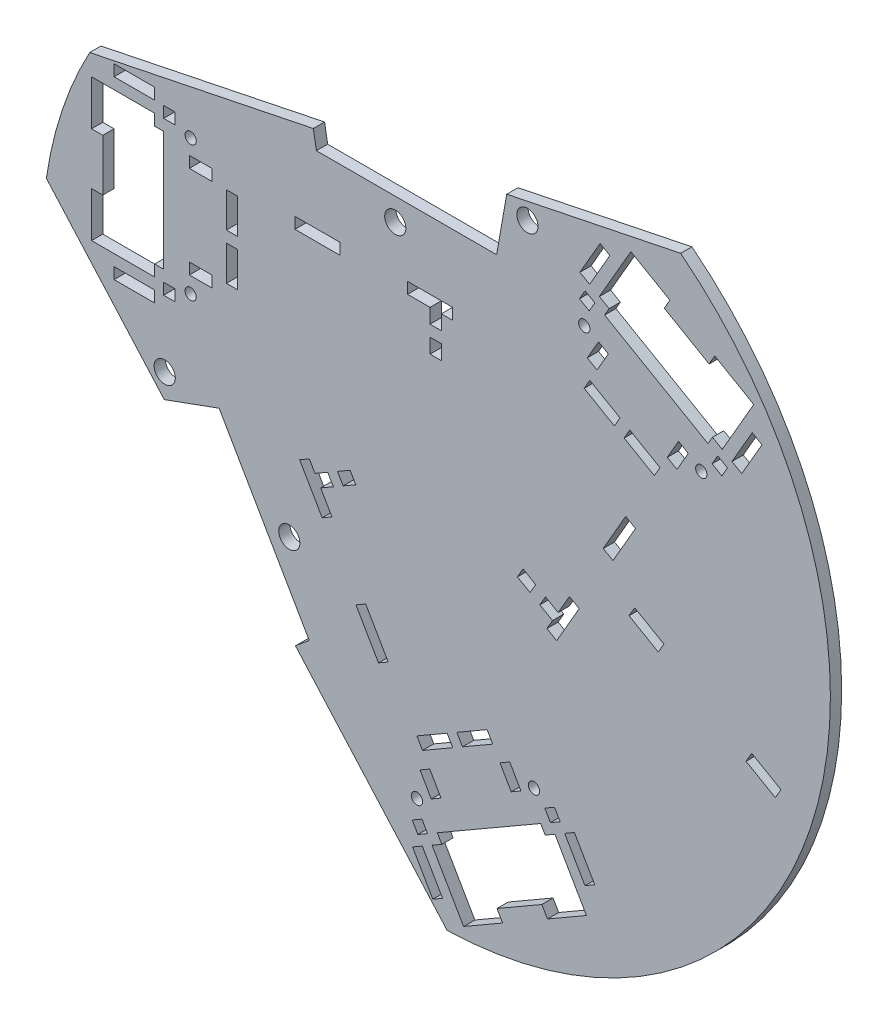
SolidWorks part; units mm, degrees
material "Balsa"
ref_plane "Plan de face" through (0, 0, 0) normal (0, 0, 1) x (1, 0, 0)
ref_plane "Plan de dessus" through (0, 0, 0) normal (0, 1, 0) x (1, 0, 0)
ref_plane "Plan de droite" through (0, 0, 0) normal (1, 0, 0) x (0, 0, -1)
sketch "Esquisse1" plane through (0, 0, 0) normal (0, 0, 1) x (1, 0, 0)
  circle A0 centre (148.0804, -12.1102) radius 175
extrude "Boss.-Extru.1" add sketch "Esquisse1" along normal blind 5
sketch "Esquisse2" plane through (0, 0, 0) normal (0, 0, -1) x (-1, 0, 0)
  line L0 (-155.3118, 53.7774) -> (-135.3118, 53.7774)
  line L1 (-150.3118, 37.2774) -> (-145.3118, 37.2774)
  line L2 (-150.3118, 37.2774) -> (-150.3118, 30.7774)
  line L3 (-150.3118, 30.7774) -> (-145.3118, 30.7774)
  line L4 (-145.3118, 37.2774) -> (-145.3118, 30.7774)
  line L5 (-105.3118, 53.7774) -> (-85.3118, 53.7774)
  line L6 (-105.3118, 53.7774) -> (-105.3118, 48.7774)
  line L7 (-105.3118, 48.7774) -> (-85.3118, 48.7774)
  line L8 (-85.3118, 53.7774) -> (-85.3118, 48.7774)
  line L9 (-59.86, 48.7774) -> (-54.86, 48.7774)
  line L10 (-59.86, 48.7774) -> (-59.86, 33.2774)
  line L11 (-59.86, 33.2774) -> (-54.86, 33.2774)
  line L12 (-54.86, 48.7774) -> (-54.86, 33.2774)
  line L13 (-59.86, 28.2774) -> (-54.86, 28.2774)
  line L14 (-59.86, 28.2774) -> (-59.86, 12.7774)
  line L15 (-59.86, 12.7774) -> (-54.86, 12.7774)
  line L16 (-54.86, 28.2774) -> (-54.86, 12.7774)
  line L17 (-48.43, 12.7774) -> (-38.43, 12.7774)
  line L18 (-48.43, 12.7774) -> (-48.43, 7.7774)
  line L19 (-48.43, 7.7774) -> (-38.43, 7.7774)
  line L20 (-38.43, 12.7774) -> (-38.43, 7.7774)
  line L21 (-32, -0.7226) -> (-27, -0.7226)
  line L22 (-32, -0.7226) -> (-32, -5.7226)
  line L23 (-32, -5.7226) -> (-27, -5.7226)
  line L24 (-27, -0.7226) -> (-27, -5.7226)
  line L25 (-23, -5.7226) -> (-5, -5.7226)
  line L26 (-23, -5.7226) -> (-23, -10.7226)
  line L27 (-23, -10.7226) -> (-5, -10.7226)
  line L28 (-5, -5.7226) -> (-5, -10.7226)
  line L29 (0, -0.7226) -> (5, -0.7226)
  line L30 (0, -0.7226) -> (0, 19.2774)
  line L31 (0, 19.2774) -> (5, 19.2774)
  line L32 (5, -0.7226) -> (5, 19.2774)
  line L33 (0, 42.2774) -> (5, 42.2774)
  line L34 (0, 42.2774) -> (0, 62.2774)
  line L35 (0, 62.2774) -> (5, 62.2774)
  line L36 (5, 42.2774) -> (5, 62.2774)
  line L37 (-23, 67.2774) -> (-5, 67.2774)
  line L38 (-23, 67.2774) -> (-23, 72.2774)
  line L39 (-23, 72.2774) -> (-5, 72.2774)
  line L40 (-5, 67.2774) -> (-5, 72.2774)
  line L41 (-27, 67.2774) -> (-32, 67.2774)
  line L42 (-27, 67.2774) -> (-27, 62.2774)
  line L43 (-27, 62.2774) -> (-32, 62.2774)
  line L44 (-32, 67.2774) -> (-32, 62.2774)
  line L45 (-38.43, 53.7774) -> (-48.43, 53.7774)
  line L46 (-38.43, 53.7774) -> (-38.43, 48.7774)
  line L47 (-38.43, 48.7774) -> (-48.43, 48.7774)
  line L48 (-48.43, 53.7774) -> (-48.43, 48.7774)
  line L49 (-135.3118, 53.7774) -> (-135.3118, 48.7774)
  line L50 (-135.3118, 48.7774) -> (-145.3118, 48.7774)
  line L51 (-135.3118, 48.7774) -> (-155.3118, 48.7774) construction
  line L52 (-145.3118, 48.7774) -> (-145.3118, 42.2774)
  line L53 (-145.3118, 42.2774) -> (-150.3118, 42.2774)
  line L54 (-150.3118, 42.2774) -> (-150.3118, 48.7774)
  line L55 (-150.3118, 48.7774) -> (-155.3118, 48.7774)
  line L56 (-155.3118, 48.7774) -> (-155.3118, 53.7774)
  line L57 (-87.4044, -38.7914) -> (-97.4044, -56.1119)
  line L58 (-104.1938, -34.8716) -> (-106.6938, -39.2017)
  line L59 (-104.1938, -34.8716) -> (-109.823, -31.6216)
  line L60 (-109.823, -31.6216) -> (-112.323, -35.9517)
  line L61 (-106.6938, -39.2017) -> (-112.323, -35.9517)
  line L62 (-112.4044, -82.0927) -> (-122.4044, -99.4132)
  line L63 (-112.4044, -82.0927) -> (-116.7345, -79.5927)
  line L64 (-116.7345, -79.5927) -> (-126.7345, -96.9132)
  line L65 (-122.4044, -99.4132) -> (-126.7345, -96.9132)
  line L66 (-139.4604, -118.9551) -> (-141.9604, -123.2852)
  line L67 (-139.4604, -118.9551) -> (-152.8838, -111.2051)
  line L68 (-152.8838, -111.2051) -> (-155.3838, -115.5352)
  line L69 (-141.9604, -123.2852) -> (-155.3838, -115.5352)
  line L70 (-157.2139, -108.7051) -> (-159.7139, -113.0352)
  line L71 (-157.2139, -108.7051) -> (-170.6373, -100.9551)
  line L72 (-170.6373, -100.9551) -> (-173.1373, -105.2852)
  line L73 (-159.7139, -113.0352) -> (-173.1373, -105.2852)
  line L74 (-176.3523, -110.8538) -> (-181.3523, -119.514)
  line L75 (-176.3523, -110.8538) -> (-180.6825, -108.3538)
  line L76 (-180.6825, -108.3538) -> (-185.6825, -117.014)
  line L77 (-181.3523, -119.514) -> (-185.6825, -117.014)
  line L78 (-196.2587, -118.3326) -> (-198.7587, -122.6627)
  line L79 (-196.2587, -118.3326) -> (-200.5888, -115.8326)
  line L80 (-200.5888, -115.8326) -> (-203.0888, -120.1627)
  line L81 (-198.7587, -122.6627) -> (-203.0888, -120.1627)
  line L82 (-205.0888, -123.6268) -> (-214.0888, -139.2153)
  line L83 (-205.0888, -123.6268) -> (-209.4189, -121.1268)
  line L84 (-209.4189, -121.1268) -> (-218.4189, -136.7153)
  line L85 (-214.0888, -139.2153) -> (-218.4189, -136.7153)
  line L86 (-212.2587, -146.0454) -> (-214.7587, -150.3755)
  line L87 (-212.2587, -146.0454) -> (-194.9382, -156.0454)
  line L88 (-194.9382, -156.0454) -> (-197.4382, -160.3755)
  line L89 (-214.7587, -150.3755) -> (-197.4382, -160.3755)
  line L90 (-175.0196, -167.5454) -> (-177.5196, -171.8755)
  line L91 (-175.0196, -167.5454) -> (-157.6991, -177.5454)
  line L92 (-157.6991, -177.5454) -> (-160.1991, -181.8755)
  line L93 (-177.5196, -171.8755) -> (-160.1991, -181.8755)
  line L94 (-141.869, -160.1268) -> (-150.869, -175.7153)
  line L95 (-141.869, -160.1268) -> (-137.5388, -162.6268)
  line L96 (-137.5388, -162.6268) -> (-146.5388, -178.2153)
  line L97 (-150.869, -175.7153) -> (-146.5388, -178.2153)
  line L98 (-139.869, -156.6627) -> (-137.369, -152.3326)
  line L99 (-139.869, -156.6627) -> (-144.1991, -154.1627)
  line L100 (-144.1991, -154.1627) -> (-141.6991, -149.8326)
  line L101 (-137.369, -152.3326) -> (-141.6991, -149.8326)
  line L102 (-145.8453, -140.014) -> (-140.8453, -131.3538)
  line L103 (-145.8453, -140.014) -> (-150.1754, -137.514)
  line L104 (-150.1754, -137.514) -> (-145.1754, -128.8538)
  line L105 (-140.8453, -131.3538) -> (-145.1754, -128.8538)
  line L106 (-97.4044, -56.1119) -> (-101.7345, -53.6119)
  line L107 (-101.7345, -53.6119) -> (-96.7345, -44.9517)
  line L108 (-96.7345, -44.9517) -> (-102.3637, -41.7017)
  line L109 (-102.3637, -41.7017) -> (-99.8637, -37.3716)
  line L110 (-99.8637, -37.3716) -> (-94.2345, -40.6216)
  line L111 (-94.2345, -40.6216) -> (-91.7345, -36.2914)
  line L112 (-91.7345, -36.2914) -> (-87.4044, -38.7914)
  line L113 (-201.5251, -51.3165) -> (-211.5251, -33.996)
  line L114 (-189.7357, -38.7364) -> (-192.2357, -34.4063)
  line L115 (-189.7357, -38.7364) -> (-184.1065, -35.4864)
  line L116 (-184.1065, -35.4864) -> (-186.6065, -31.1563)
  line L117 (-192.2357, -34.4063) -> (-186.6065, -31.1563)
  line L118 (-226.5251, -8.0153) -> (-236.5251, 9.3053)
  line L119 (-226.5251, -8.0153) -> (-222.195, -5.5153)
  line L120 (-222.195, -5.5153) -> (-232.195, 11.8053)
  line L121 (-236.5251, 9.3053) -> (-232.195, 11.8053)
  line L122 (-244.9209, 33.8472) -> (-247.4209, 38.1773)
  line L123 (-244.9209, 33.8472) -> (-231.4975, 41.5972)
  line L124 (-231.4975, 41.5972) -> (-233.9975, 45.9273)
  line L125 (-247.4209, 38.1773) -> (-233.9975, 45.9273)
  line L126 (-227.1673, 44.0972) -> (-229.6673, 48.4273)
  line L127 (-227.1673, 44.0972) -> (-213.7439, 51.8472)
  line L128 (-213.7439, 51.8472) -> (-216.2439, 56.1773)
  line L129 (-229.6673, 48.4273) -> (-216.2439, 56.1773)
  line L130 (-219.4589, 61.7458) -> (-224.4589, 70.4061)
  line L131 (-219.4589, 61.7458) -> (-215.1288, 64.2458)
  line L132 (-215.1288, 64.2458) -> (-220.1288, 72.9061)
  line L133 (-224.4589, 70.4061) -> (-220.1288, 72.9061)
  line L134 (-215.9826, 82.7246) -> (-218.4826, 87.0547)
  line L135 (-215.9826, 82.7246) -> (-211.6525, 85.2246)
  line L136 (-211.6525, 85.2246) -> (-214.1525, 89.5547)
  line L137 (-218.4826, 87.0547) -> (-214.1525, 89.5547)
  line L138 (-216.1525, 93.0188) -> (-225.1525, 108.6073)
  line L139 (-216.1525, 93.0188) -> (-211.8223, 95.5188)
  line L140 (-211.8223, 95.5188) -> (-220.8223, 111.1073)
  line L141 (-225.1525, 108.6073) -> (-220.8223, 111.1073)
  line L142 (-231.9826, 110.4374) -> (-234.4826, 114.7676)
  line L143 (-231.9826, 110.4374) -> (-249.3031, 100.4374)
  line L144 (-249.3031, 100.4374) -> (-251.8031, 104.7676)
  line L145 (-234.4826, 114.7676) -> (-251.8031, 104.7676)
  line L146 (-269.2217, 88.9374) -> (-271.7217, 93.2676)
  line L147 (-269.2217, 88.9374) -> (-286.5422, 78.9374)
  line L148 (-286.5422, 78.9374) -> (-289.0422, 83.2676)
  line L149 (-271.7217, 93.2676) -> (-289.0422, 83.2676)
  line L150 (-279.3723, 56.5188) -> (-288.3723, 72.1073)
  line L151 (-279.3723, 56.5188) -> (-283.7025, 54.0188)
  line L152 (-283.7025, 54.0188) -> (-292.7025, 69.6073)
  line L153 (-288.3723, 72.1073) -> (-292.7025, 69.6073)
  line L154 (-277.3723, 53.0547) -> (-274.8723, 48.7246)
  line L155 (-277.3723, 53.0547) -> (-273.0422, 55.5547)
  line L156 (-273.0422, 55.5547) -> (-270.5422, 51.2246)
  line L157 (-274.8723, 48.7246) -> (-270.5422, 51.2246)
  line L158 (-259.966, 49.9061) -> (-254.966, 41.2458)
  line L159 (-259.966, 49.9061) -> (-255.6359, 52.4061)
  line L160 (-255.6359, 52.4061) -> (-250.6359, 43.7458)
  line L161 (-254.966, 41.2458) -> (-250.6359, 43.7458)
  line L162 (-211.5251, -33.996) -> (-207.195, -31.496)
  line L163 (-207.195, -31.496) -> (-202.195, -40.1563)
  line L164 (-202.195, -40.1563) -> (-196.5658, -36.9063)
  line L165 (-196.5658, -36.9063) -> (-194.0658, -41.2364)
  line L166 (-194.0658, -41.2364) -> (-199.695, -44.4864)
  line L167 (-199.695, -44.4864) -> (-197.195, -48.8165)
  line L168 (-197.195, -48.8165) -> (-201.5251, -51.3165)
  point P204 (-148.0804, -12.1102)
  dimension "D1" = 3
extrude "Enlèv. mat.-Extru.1" cut sketch "Esquisse2" against normal blind 5
sketch "Esquisse3" plane through (0, 0, 0) normal (0, 0, -1) x (-1, 0, 0)
  line L0 (-59.86, 33.2774) -> (-59.86, 28.2774) construction
  line L1 (-59.86, 30.7774) -> (32.4397, 30.7774) construction
  line L2 (0, -0.7226) -> (-23, -0.7226)
  line L3 (-23, -0.7226) -> (-23, 4.2774)
  line L4 (-23, 4.2774) -> (-27, 4.2774)
  line L5 (-23, 57.2774) -> (-27, 57.2774)
  line L6 (-23, 62.2774) -> (-23, 57.2774)
  line L7 (0, 62.2774) -> (-23, 62.2774)
  line L8 (-27, 57.2774) -> (-27, 4.2774)
  line L9 (0, -0.7226) -> (0, 62.2774)
  line L10 (-212.2587, -146.0454) -> (-200.7587, -126.1268)
  line L11 (-200.7587, -126.1268) -> (-196.4286, -128.6268)
  line L12 (-196.4286, -128.6268) -> (-194.4286, -125.1627)
  line L13 (-150.5292, -155.1268) -> (-148.5292, -151.6627)
  line L14 (-146.1991, -157.6268) -> (-150.5292, -155.1268)
  line L15 (-157.6991, -177.5454) -> (-146.1991, -157.6268)
  line L16 (-148.5292, -151.6627) -> (-194.4286, -125.1627)
  line L17 (-212.2587, -146.0454) -> (-157.6991, -177.5454)
  line L18 (-152.8838, -111.2051) -> (-157.2139, -108.7051) construction
  line L19 (-155.0489, -109.9551) -> (-201.1987, -189.889) construction
  line L20 (-231.9826, 110.4374) -> (-220.4826, 90.5188)
  line L21 (-220.4826, 90.5188) -> (-224.8127, 88.0188)
  line L22 (-224.8127, 88.0188) -> (-222.8127, 84.5547)
  line L23 (-270.7121, 61.5188) -> (-268.7121, 58.0547)
  line L24 (-275.0422, 59.0188) -> (-270.7121, 61.5188)
  line L25 (-286.5422, 78.9374) -> (-275.0422, 59.0188)
  line L26 (-268.7121, 58.0547) -> (-222.8127, 84.5547)
  line L27 (-231.9826, 110.4374) -> (-286.5422, 78.9374)
  line L28 (-231.4975, 41.5972) -> (-227.1673, 44.0972) construction
  line L29 (-229.3324, 42.8472) -> (-275.4822, 122.781) construction
  point P42 (-148.0804, -12.1102)
  dimension "D1" = 5
  dimension "D2" = 4
  dimension "D3" = 23
  dimension "D4" = 3
extrude "Enlèv. mat.-Extru.2" cut sketch "Esquisse3" against normal blind 5
sketch "Esquisse4" plane through (0, 0, 0) normal (0, 0, -1) x (-1, 0, 0)
  line L0 (-32, 67.2774) -> (-32, 62.2774) construction
  line L1 (-38.43, 53.7774) -> (-48.43, 53.7774) construction
  line L2 (-27, 30.7774) -> (-93.5454, 30.7774) construction
  line L3 (-27, 57.2774) -> (-27, 4.2774) construction
  line L4 (-171.4789, -138.4127) -> (-138.2062, -80.7827) construction
  line L5 (-245.7624, 71.3047) -> (-212.4897, 13.6748) construction
  circle A0 centre (-39, 60.7774) radius 2.5
  circle A1 centre (-39, 0.7774) radius 2.5
  circle A2 centre (-139.4981, -143.0204) radius 2.5
  circle A3 centre (-191.4596, -113.0204) radius 2.5
  circle A4 centre (-265.7432, 45.9124) radius 2.5
  circle A5 centre (-213.7816, 75.9124) radius 2.5
  point P27 (-148.0804, -12.1102)
  dimension "D1" = 7
  dimension "D2" = 7
  dimension "D3" = 3
extrude "Enlèv. mat.-Extru.3" cut sketch "Esquisse4" against normal blind 5
sketch "Esquisse5" plane through (0, 0, 0) normal (0, 0, -1) x (-1, 0, 0)
  line L0 (9.513, 70.4436) -> (-93.4749, 91.6327)
  line L1 (-315.6991, 137.3538) -> (-290.787, 258.4375)
  line L2 (-290.787, 258.4375) -> (34.4251, 191.5273)
  line L3 (34.4251, 191.5273) -> (9.513, 70.4436)
  line L4 (-233.6714, -25.6375) -> (-246.6617, -33.1375)
  line L5 (-179.3609, 109.3031) -> (-315.6991, 137.3538)
  line L6 (-94.86, 83.7774) -> (-174.86, 83.7774)
  line L7 (-174.86, 83.7774) -> (-179.3609, 109.3031)
  line L8 (-233.6714, -25.6375) -> (-236.1714, -21.3074)
  line L9 (-93.4749, 91.6327) -> (-94.86, 83.7774)
  line L10 (-155.3834, -189.8669) -> (-85.5392, -111.2714)
  line L11 (65.1685, 58.3199) -> (157.574, -23.7965)
  line L12 (26.9196, -12.1102) -> (-148.0804, -12.1102) construction
  line L13 (157.574, -23.7965) -> (-62.9779, -271.9834)
  line L14 (-62.9779, -271.9834) -> (-155.3834, -189.8669)
  line L15 (-246.6617, -33.1375) -> (-249.1617, -28.8074)
  line L16 (-27.2932, -45.7272) -> (65.1685, 58.3199)
  line L17 (-91.6495, -106.1442) -> (-51.6495, -36.8622)
  line L18 (-51.6495, -36.8622) -> (-27.2932, -45.7272)
  line L19 (-236.1714, -21.3074) -> (-249.1617, -28.8074)
  line L20 (-85.5392, -111.2714) -> (-91.6495, -106.1442)
  line L21 (-148.0804, -12.1102) -> (-235.5804, -163.6646) construction
  line L22 (-93.4749, 91.6327) -> (-179.3609, 109.3031) construction
  line L23 (-139.86, 83.7774) -> (-139.86, 101.1761) construction
  line L24 (-285.6329, -55.6375) -> (-298.6233, -63.1375)
  line L25 (-285.6329, -55.6375) -> (-288.1329, -51.3074)
  line L26 (-298.6233, -63.1375) -> (-301.1233, -58.8074)
  line L27 (-288.1329, -51.3074) -> (-301.1233, -58.8074)
  line L28 (-211.5251, -33.996) -> (-201.5251, -51.3165) construction
  line L29 (-283.7025, 54.0188) -> (-279.3723, 56.5188) construction
  circle A0 centre (-188.5408, 103.7774) radius 4.7
  circle A1 centre (-129.86, 73.7774) radius 4.7
  circle A2 centre (-27.4886, -35.0143) radius 4.7
  circle A3 centre (-82.8098, -70.8333) radius 4.7
  point P15 (-148.0804, -12.1102)
  point P35 (-148.0804, -12.1102)
  dimension "D2" = 9.4
  dimension "D3" = 9.4
  dimension "D4" = 100
  dimension "D5" = 100
  dimension "D6" = 5
  dimension "D7" = 45
  dimension "D8" = 15
  dimension "D9" = 80
  dimension "D10" = 35
  dimension "D11" = 85.8876
  dimension "D12" = 58.6808
  dimension "D13" = 30
  dimension "D14" = 10
  dimension "D15" = 11.626
  dimension "D16" = 18.2204
  dimension "D18" = 17.3986
  dimension "D19" = 15
  dimension "D20" = 45
  dimension "D21" = 15
  dimension "D22" = 89
  dimension "D17" = 2
extrude "Enlèv. mat.-Extru.4" cut sketch "Esquisse5" against normal blind 5
